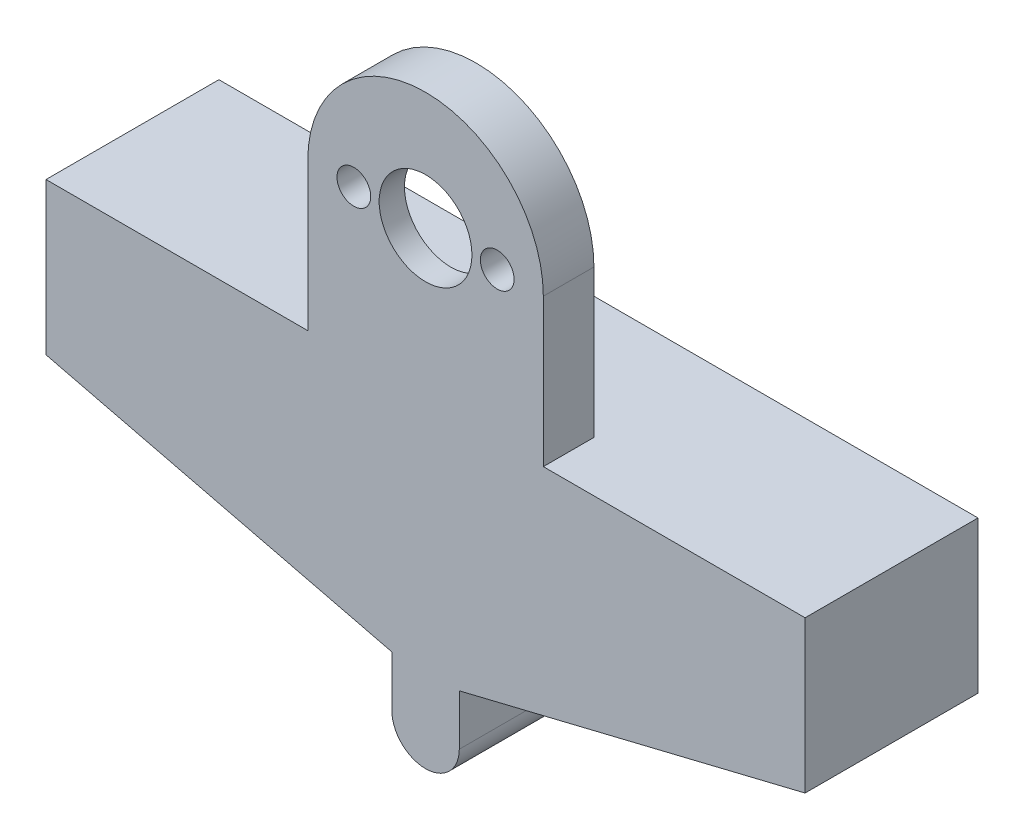
SolidWorks part; units mm, degrees
ref_plane "Front Plane" through (0, 0, 0) normal (0, 0, 1) x (1, 0, 0)
ref_plane "Top Plane" through (0, 0, 0) normal (0, 1, 0) x (1, 0, 0)
ref_plane "Right Plane" through (0, 0, 0) normal (1, 0, 0) x (0, 0, -1)
sketch "Sketch1" plane through (0, 0, 0) normal (0, 0, 1) x (1, 0, 0)
  line L0 (4, -9) -> (-4, -9)
  line L1 (-45, -9) -> (45, -9)
  line L2 (-45, -9) -> (-45, 9)
  line L3 (-45, 9) -> (45, 9)
  line L4 (45, -9) -> (45, 9)
  line L5 (-45, -9) -> (45, 9) construction
  line L6 (-45, 9) -> (45, -9) construction
  line L7 (-22.5, -3) -> (-7.5, -3)
  line L8 (-22.5, -3) -> (-22.5, 3)
  line L9 (-22.5, 3) -> (-7.5, 3)
  line L10 (-7.5, -3) -> (-7.5, 3)
  line L11 (-22.5, -3) -> (-7.5, 3) construction
  line L12 (-22.5, 3) -> (-7.5, -3) construction
  line L13 (7.5, -3) -> (22.5, -3)
  line L14 (7.5, -3) -> (7.5, 3)
  line L15 (7.5, 3) -> (22.5, 3)
  line L16 (22.5, -3) -> (22.5, 3)
  line L17 (7.5, -3) -> (22.5, 3) construction
  line L18 (7.5, 3) -> (22.5, -3) construction
  line L19 (4, -9) -> (4, -29)
  line L20 (-4, -9) -> (-4, -29)
  line L21 (4, -29) -> (-4, -29)
  line L22 (4, -19) -> (45, -9)
  line L23 (-4, -19) -> (-45, -9)
  point P0 (0, 0)
  point P6 (-15, 0)
  point P11 (15, 0)
  dimension "D1" = 90
  dimension "D2" = 18
  dimension "D3" = 6
  dimension "D4" = 6
  dimension "D5" = 6
  dimension "D6" = 6
  dimension "D7" = 15
  dimension "D8" = 15
  dimension "D9" = 7.5
  dimension "D10" = 7.5
  dimension "D11" = 8
  dimension "D12" = 4
  dimension "D13" = 20
extrude "Boss-Extrude1" add sketch "Sketch1" along normal blind 14 contours L1 L4 L3 L2 L0 L16 L13 L14 L15 L10 L7 L8 L9 | L21 L19 L0 L20 | L7 L10 L9 L8 | L13 L16 L15 L14 | L19 L22 L1 | L23 L20 L1 region at (0, -19, 0) region at (0, 0, 0) region at (17.6667, -12.3333, 0) region at (-17.6667, -12.3333, 0) region at (-15, 0, 0) region at (15, 0, 0)
sketch "Sketch3" plane through (0, 0, 0) normal (0, 0, 1) x (1, 0, 0)
  line L0 (4, -9) -> (-4, -9)
  line L1 (-45, -9) -> (45, -9)
  line L2 (-45, -9) -> (-45, 9)
  line L3 (-45, 9) -> (45, 9)
  line L4 (45, -9) -> (45, 9)
  line L5 (-45, -9) -> (45, 9) construction
  line L6 (-45, 9) -> (45, -9) construction
  line L7 (-22.5, -3) -> (-7.5, -3)
  line L8 (-22.5, -3) -> (-22.5, 3)
  line L9 (-22.5, 3) -> (-7.5, 3)
  line L10 (-7.5, -3) -> (-7.5, 3)
  line L11 (-22.5, -3) -> (-7.5, 3) construction
  line L12 (-22.5, 3) -> (-7.5, -3) construction
  line L13 (7.5, -3) -> (22.5, -3)
  line L14 (7.5, -3) -> (7.5, 3)
  line L15 (7.5, 3) -> (22.5, 3)
  line L16 (22.5, -3) -> (22.5, 3)
  line L17 (7.5, -3) -> (22.5, 3) construction
  line L18 (7.5, 3) -> (22.5, -3) construction
  line L19 (4, -9) -> (4, -29)
  line L20 (-4, -9) -> (-4, -29)
  line L21 (4, -29) -> (-4, -29)
  point P0 (0, 0)
  point P6 (-15, 0)
  point P11 (15, 0)
  dimension "D1" = 90
  dimension "D2" = 18
  dimension "D3" = 6
  dimension "D4" = 6
  dimension "D5" = 6
  dimension "D6" = 6
  dimension "D7" = 15
  dimension "D8" = 15
  dimension "D9" = 7.5
  dimension "D10" = 7.5
  dimension "D11" = 8
  dimension "D12" = 4
  dimension "D13" = 20
extrude "Boss-Extrude2" add sketch "Sketch3" against normal blind 6.5 contours L1 L4 L3 L2 L0 L16 L13 L14 L15 L10 L7 L8 L9 | L21 L19 L0 L20 region at (0, -19, 0) region at (0, 0, 0)
fillet "Fillet1" radius 4 2 edges at (-4, -29, 3.75) (4, -29, 3.75)
sketch "Sketch4" plane through (0, 0, 14) normal (0, 0, 1) x (1, 0, 0)
  line L0 (-13.9645, 26.5) -> (-13.9645, 9)
  line L1 (-45, 9) -> (45, 9) construction
  line L2 (13.9645, 26.5) -> (13.9645, 9)
  circle A0 centre (0, 26.5) radius 5.5
  circle A1 centre (8.5, 26.5) radius 2
  circle A2 centre (-8.5, 26.5) radius 2
  circle A3 centre (0, 26.5) radius 13.9645
  line M8 (45, 9) -> (-45, 9)
  dimension "D1" = 8.5
  dimension "D2" = 8.5
  dimension "D3" = 0
  dimension "D4" = 17.5
extrude "Boss-Extrude3" add sketch "Sketch4" against normal blind 6 contours A3 A0 A1 A2 | A3 L2 M8 | A3 L0 M8 region at (0, 12.2059, 14) region at (0, 40.0695, 14)
sketch "Sketch5" plane through (0, 0, 8) normal (0, 0, -1) x (-1, 0, 0)
  circle A2 centre (0, 26.5) radius 12.05
extrude "Cut-Extrude1" cut sketch "Sketch5" against normal blind 3
